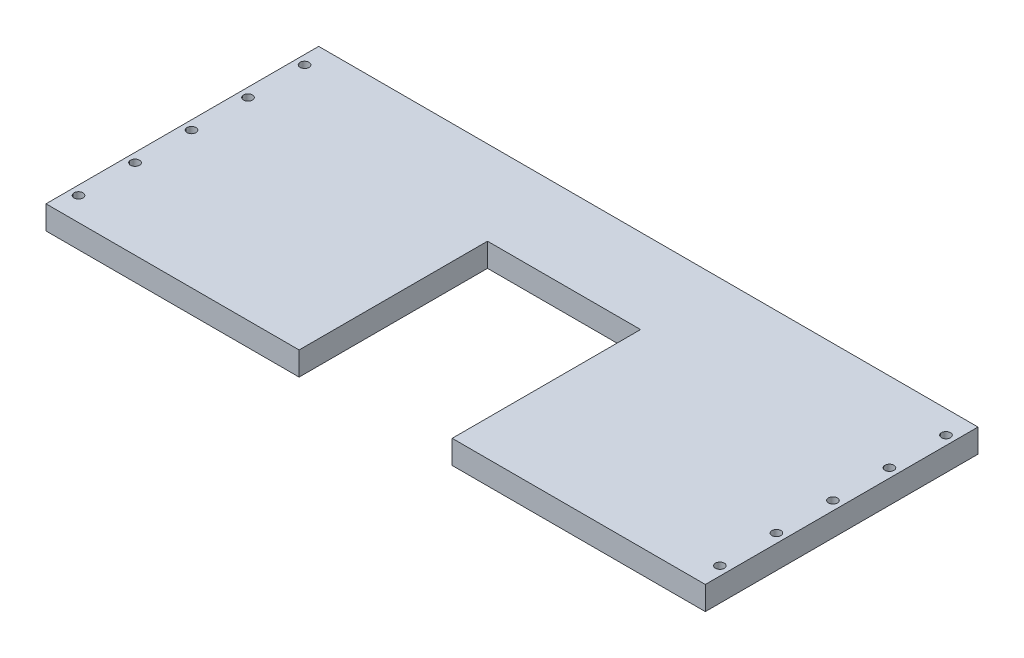
SolidWorks part; units mm, degrees
ref_plane "Front Plane" through (0, 0, 0) normal (0, 0, 1) x (1, 0, 0)
ref_plane "Top Plane" through (0, 0, 0) normal (0, 1, 0) x (1, 0, 0)
ref_plane "Right Plane" through (0, 0, 0) normal (1, 0, 0) x (0, 0, -1)
sketch "Sketch1" plane through (0, 0, 0) normal (0, 1, 0) x (1, 0, 0)
  line L0 (-41.275, -101.6) -> (-41.275, 0)
  line L1 (-177.8, 45.466) -> (177.8, 45.466)
  line L2 (-177.8, 45.466) -> (-177.8, -101.6)
  line L3 (-177.8, -101.6) -> (-41.275, -101.6)
  line L4 (177.8, 45.466) -> (177.8, -101.6)
  line L5 (0, 45.466) -> (0, 0) construction
  line L6 (0, 0) -> (0, 304.3208) construction
  line L7 (41.275, -101.6) -> (41.275, 0)
  line L8 (-41.275, 0) -> (41.275, 0)
  line L9 (41.275, -101.6) -> (177.8, -101.6)
  dimension "D1" = 355.6
  dimension "D2" = 147.066
  dimension "D3" = 82.55
  dimension "4" = 101.6
extrude "Boss-Extrude1" add sketch "Sketch1" along normal blind 12.7
sketch "Sketch2" plane through (0, 12.7, 0) normal (0, 1, 0) x (1, 0, 0)
  line L0 (177.8, -101.6) -> (177.8, 45.466) construction
  line L1 (41.275, -101.6) -> (177.8, -101.6) construction
  circle A0 centre (172.974, -88.9) radius 2.413
  dimension "D1" = 4.826
  dimension "D3" = 12.7
  dimension "D2" = 4.826
extrude "Cut-Extrude1" cut sketch "Sketch2" against normal through all contours A0
pattern_linear "LPattern2" count 2 spacing 345.948 along (-1, 0, 0) count 5 spacing 30.48 along (0, 0, -1) of "Cut-Extrude1"
